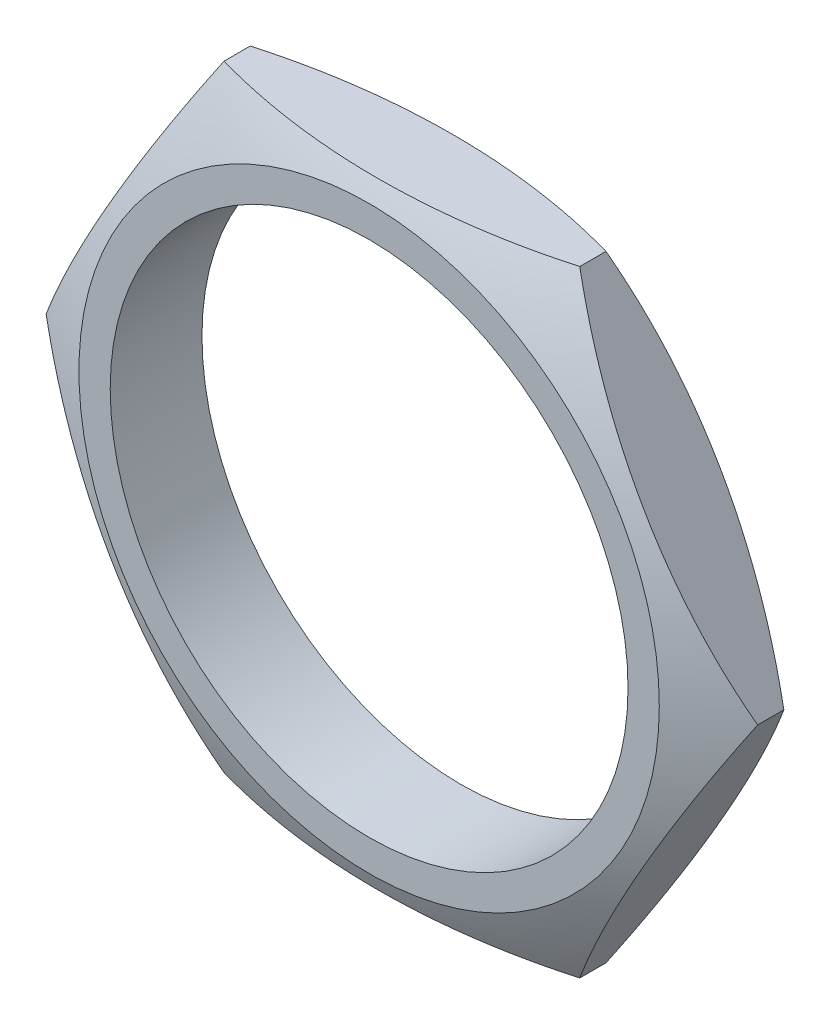
SolidWorks part; units mm, degrees
ref_plane "Plan de face" through (0, 0, 0) normal (0, 0, 1) x (1, 0, 0)
ref_plane "Plan de dessus" through (0, 0, 0) normal (0, 1, 0) x (1, 0, 0)
ref_plane "Plan de droite" through (0, 0, 0) normal (1, 0, 0) x (0, 0, -1)
sketch "Esquisse1" plane through (0, 0, 0) normal (0, 0, 1) x (1, 0, 0)
  line L1 (10.8542, 0) -> (5.4271, 9.4)
  line L2 (5.4271, 9.4) -> (-5.4271, 9.4)
  line L3 (-5.4271, 9.4) -> (-10.8542, 0)
  line L4 (-10.8542, 0) -> (-5.4271, -9.4)
  line L5 (-5.4271, -9.4) -> (5.4271, -9.4)
  line L6 (5.4271, -9.4) -> (10.8542, 0)
  circle A0 centre (0, 0) radius 7.9
  circle A1 centre (0, 0) radius 9.4 construction
  point P3 (0, 0)
  dimension "D2" = 15.8
  dimension "D1" = 18.8
extrude "Boss.-Extru.1" add sketch "Esquisse1" along normal mid plane 2.8
sketch "Esquisse2" plane through (0, 0, 0) normal (0, 1, 0) x (1, 0, 0)
  line L1 (-10.8542, -1.4) -> (-10.8542, 1.4) construction
  line L2 (10.8542, -1.4) -> (10.8542, 1.4) construction
  line L3 (-5.4271, 1.4) -> (-10.8542, 1.4) construction
  line L4 (0, 0) -> (0, 7.365) construction
  line L5 (-10.8542, 0.4) -> (-10.8542, 1.4)
  line L6 (-10.8542, 1.4) -> (10.8542, 1.4)
  line L7 (10.8542, 1.4) -> (10.8542, 0.4)
  arc A0 (-10.8542, 0.4) -> (10.8542, 0.4) centre (0, -18.8084) cw
  point P7 (-8.8542, 1.4)
  dimension "D1" = 1
  dimension "D2" = 2
revolve "Enlèvement de matière-Révolution1" cut sketch "Esquisse2" angle 360 about L4 region at (-10.202, 0, -1.0736)
mirror "Symétrie1" about plane through (0, 0, 0) normal (0, 0, 1) of "Enlèvement de matière-Révolution1"
